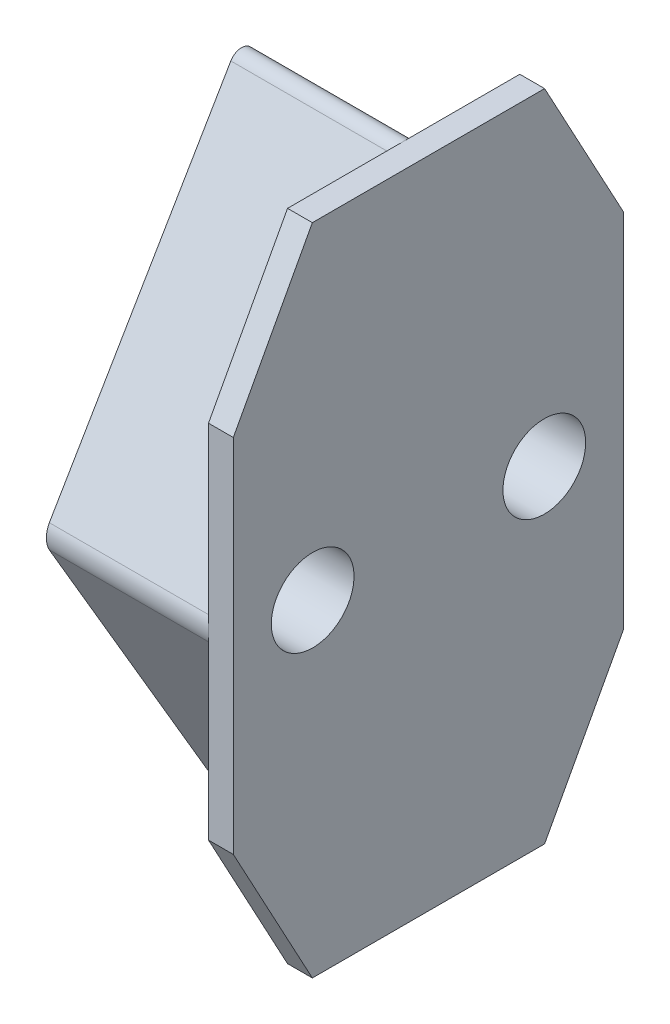
SolidWorks part; units mm, degrees
ref_plane "Front" through (0, 0, 0) normal (0, 0, 1) x (1, 0, 0)
ref_plane "Top" through (0, 0, 0) normal (0, 1, 0) x (1, 0, 0)
ref_plane "Right" through (0, 0, 0) normal (1, 0, 0) x (0, 0, -1)
sketch "Sketch1" plane through (0, 0, 0) normal (1, 0, 0) x (0, 0, -1)
  line L1 (0, -28.2575) -> (15.24, 0)
  line L2 (0, -28.2575) -> (-15.24, 0)
  line L3 (-15.24, 0) -> (0, 28.2575)
  line L4 (15.24, 0) -> (0, 28.2575)
  line L5 (0, -28.2575) -> (0, 28.2575) construction
  line L6 (-15.24, 0) -> (15.24, 0) construction
  point P0 (0, 0)
  dimension "D1" = 30.48
  dimension "D2" = 56.515
extrude "Boss-Extrude1" add sketch "Sketch1" along normal blind 12.446
sketch "Sketch6" plane through (12.446, 0, 0) normal (1, 0, 0) x (0, 0, -1)
  line L14 (-22.4547, 0) -> (0, -41.6347)
  line L15 (0, -41.6347) -> (22.4547, 0)
  line L16 (22.4547, 0) -> (0, 41.6347)
  line L17 (0, 41.6347) -> (-22.4547, 0)
  line L18 (-22.4547, 0) -> (0, -41.6347)
  line L19 (0, -41.6347) -> (22.4547, 0)
  line L20 (22.4547, 0) -> (0, 41.6347)
  line L21 (0, 41.6347) -> (-22.4547, 0)
  dimension "D1" = 6.35
extrude "Boss-Extrude3" add sketch "Sketch6" along normal blind 1.905
fillet "Fillet1" radius 1.905 8 edges at (13.3985, 41.6347, 0) (13.3985, 0, 22.4547) (13.3985, -41.6347, 0) (13.3985, 0, -22.4547) (6.223, -28.2575, 0) (6.223, 0, -15.24) (6.223, 0, 15.24) (6.223, 28.2575, 0)
sketch "Sketch7" plane through (0, 0, 0) normal (0, 1, 0) x (1, 0, 0)
  line L0 (0, 0) -> (25.2725, 0) construction
  line L1 (14.351, 0) -> (14.351, -10.3712) construction
  line L3 (4.826, -1.905) -> (4.826, 1.905) construction
  line L4 (1.651, -1.905) -> (1.651, 1.905)
  line L5 (8.001, -1.905) -> (8.001, 1.905)
  line L6 (14.351, -1.6767) -> (14.351, 1.6767) construction
  arc A1 (1.651, -1.905) -> (8.001, -1.905) centre (4.826, -1.905) ccw
  arc A2 (8.001, 1.905) -> (1.651, 1.905) centre (4.826, 1.905) ccw
  point P7 (4.826, 0)
  dimension "D1" = 6.35
  dimension "D2" = 10.16
  dimension "D3" = 6.35
revolve "Cut-Revolve2" [suppressed] cut sketch "Sketch7" angle 360 about L1
sketch "Sketch8" plane through (14.351, 0, 0) normal (1, 0, 0) x (0, 0, -1)
  line L0 (0, 0) -> (8.89, 0) construction
  line L1 (0, 0) -> (0, 3.2594) construction
  circle A0 centre (8.89, 0) radius 3.937
  circle A1 centre (-8.89, 0) radius 3.937
  dimension "D2" = 7.874
  dimension "D1" = 8.89
extrude "Cut-Extrude3" [suppressed] cut sketch "Sketch8" against normal blind 5.08
sketch "Sketch9" [suppressed] plane through (9.271, 0, 0) normal (1, 0, 0) x (0, 0, -1)
  line L0 (0, 0) -> (0, 4.0921) construction
  circle A0 centre (8.89, 0) radius 2.5527
  circle A1 centre (-8.89, 0) radius 2.5527
  dimension "D1" = 5.1054
extrude "Cut-Extrude4" [suppressed] cut sketch "Sketch9" against normal through all
sketch "Sketch10" [suppressed] plane through (15.875, 0, 0) normal (1, 0, 0) x (0, 0, -1)
  line L0 (0, 0) -> (0, 8.2156) construction
  line L1 (13.6525, 2.7496) -> (8.89, 5.4993)
  line L2 (8.89, 5.4993) -> (4.1275, 2.7496)
  line L3 (4.1275, 2.7496) -> (4.1275, -2.7496)
  line L4 (4.1275, -2.7496) -> (8.89, -5.4993)
  line L5 (8.89, -5.4993) -> (13.6525, -2.7496)
  line L6 (13.6525, -2.7496) -> (13.6525, 2.7496)
  line L7 (-13.6525, -2.7496) -> (-13.6525, 2.7496)
  line L8 (-8.89, -5.4993) -> (-13.6525, -2.7496)
  line L9 (-4.1275, -2.7496) -> (-8.89, -5.4993)
  line L10 (-4.1275, 2.7496) -> (-4.1275, -2.7496)
  line L11 (-8.89, 5.4993) -> (-4.1275, 2.7496)
  line L12 (-13.6525, 2.7496) -> (-8.89, 5.4993)
  circle A0 centre (8.89, 0) radius 4.7625 construction
  circle A1 centre (-8.89, 0) radius 4.7625 construction
  point P1 (13.6525, 0)
  dimension "D1" = 9.525
sketch "Sketch11" plane through (14.351, 0, 0) normal (1, 0, 0) x (0, 0, -1)
  line L0 (0, 0) -> (8.89, 0) construction
  line L1 (0, 0) -> (0, 10.0261) construction
  circle A0 centre (8.89, 0) radius 3.175
  circle A1 centre (-8.89, 0) radius 3.175
  dimension "D2" = 6.35
  dimension "D1" = 8.89
extrude "Cut-Extrude6" cut sketch "Sketch11" against normal through all
sketch "Sketch12" plane through (12.446, 0, 0) normal (-1, 0, 0) x (0, 0, 1)
  line L0 (-14.9806, -13.8581) -> (-14.9806, 13.8581)
  line L1 (-1.6767, -38.5258) -> (-21.9669, -0.9043) construction
  line L2 (-21.9669, 0.9043) -> (-1.6767, 38.5258) construction
  line L4 (14.9806, -13.8581) -> (14.9806, 13.8581)
  line L5 (21.9669, -0.9043) -> (1.6767, -38.5258) construction
  line L6 (1.6767, 38.5258) -> (21.9669, 0.9043) construction
  line L7 (-14.9806, -13.8581) -> (-21.9669, -0.9043)
  line L8 (21.9669, -0.9043) -> (14.9806, -13.8581)
  line L9 (14.9806, 13.8581) -> (21.9669, 0.9043)
  line L10 (-21.9669, 0.9043) -> (-14.9806, 13.8581)
  arc A0 (-14.7523, 0.9043) -> (-14.7523, -0.9043) centre (-13.0756, 0) ccw construction
  arc A3 (21.9669, -0.9043) -> (21.9669, 0.9043) centre (20.2903, 0) ccw construction
  arc A4 (-21.9669, 0.9043) -> (-21.9669, -0.9043) centre (-20.2903, 0) ccw construction
  arc A5 (21.9669, -0.9043) -> (21.9669, 0.9043) centre (20.2903, 0) ccw
  arc A6 (-21.9669, 0.9043) -> (-21.9669, -0.9043) centre (-20.2903, 0) ccw
  arc A8 (14.7523, -0.9043) -> (14.7523, 0.9043) centre (13.0756, 0) ccw construction
  point P7 (-14.9806, 0)
  point P11 (14.9806, 0)
extrude "Cut-Extrude7" cut sketch "Sketch12" against normal through all
sketch "Sketch13" [suppressed] plane through (9.271, 0, 0) normal (1, 0, 0) x (0, 0, -1)
  line L1 (5.8927, 2.5527) -> (11.8873, 2.5527)
  line L3 (5.8927, -2.5527) -> (11.8873, -2.5527)
  line L5 (-11.8873, 2.5527) -> (-5.8927, 2.5527)
  line L7 (-11.8873, -2.5527) -> (-5.8927, -2.5527)
  circle A0 centre (8.89, 0) radius 3.937 construction
  circle A1 centre (8.89, 0) radius 3.937 construction
  circle A2 centre (-8.89, 0) radius 3.937 construction
  circle A3 centre (-8.89, 0) radius 2.5527 construction
  circle A4 centre (8.89, 0) radius 2.5527 construction
  circle A5 centre (-8.89, 0) radius 3.937 construction
  arc A6 (5.8927, 2.5527) -> (5.8927, -2.5527) centre (8.89, 0) ccw
  arc A7 (-11.8873, 2.5527) -> (-11.8873, -2.5527) centre (-8.89, 0) ccw
  arc A8 (-5.8927, -2.5527) -> (-5.8927, 2.5527) centre (-8.89, 0) ccw
  arc A9 (11.8873, -2.5527) -> (11.8873, 2.5527) centre (8.89, 0) ccw
extrude "Cut-Extrude8" [suppressed] cut sketch "Sketch13" against normal blind 0.2
sketch "Sketch14" [suppressed] plane through (9.071, 0, 0) normal (1, 0, 0) x (0, 0, -1)
  line L0 (11.8873, 2.5527) -> (5.8927, 2.5527) construction
  line L1 (6.3373, 2.5527) -> (11.4427, 2.5527)
  line L2 (6.3373, 2.5527) -> (6.3373, -2.5527)
  line L3 (6.3373, -2.5527) -> (11.4427, -2.5527)
  line L4 (11.4427, 2.5527) -> (11.4427, -2.5527)
  line L5 (8.89, -2.5527) -> (11.8873, -2.5527) construction
  line L6 (-5.8927, 2.5527) -> (-11.8873, 2.5527) construction
  line L7 (-11.4427, 2.5527) -> (-6.3373, 2.5527)
  line L8 (-11.4427, 2.5527) -> (-11.4427, -2.5527)
  line L9 (-11.4427, -2.5527) -> (-6.3373, -2.5527)
  line L10 (-6.3373, 2.5527) -> (-6.3373, -2.5527)
  line L11 (-11.8873, -2.5527) -> (-5.8927, -2.5527) construction
  arc A0 (-8.89, 2.5527) -> (-8.89, -2.5527) centre (-8.89, 0) ccw construction
  arc A1 (-8.89, -2.5527) -> (-8.89, 2.5527) centre (-8.89, 0) ccw construction
  arc A2 (8.89, 2.5527) -> (8.89, -2.5527) centre (8.89, 0) ccw construction
  arc A3 (8.89, -2.5527) -> (8.89, 2.5527) centre (8.89, 0) ccw construction
extrude "Cut-Extrude9" [suppressed] cut sketch "Sketch14" against normal blind 0.2
sketch "Sketch15" plane through (0, 0, 0) normal (-1, 0, 0) x (0, 0, 1)
  line L0 (-14.7523, -0.9043) -> (0, -26.035)
  line L1 (0, -26.035) -> (14.7523, -0.9043)
  line L2 (14.7523, 0.9043) -> (0, 26.035)
  line L3 (0, 26.035) -> (-14.7523, 0.9043)
  line L4 (1.6767, 25.1486) -> (14.7523, 0.9043) construction
  line L5 (-14.7523, 0.9043) -> (-1.6767, 25.1486) construction
  line L6 (-14.7523, 0.9043) -> (-1.6767, 25.1486)
  line L7 (1.6767, 25.1486) -> (14.7523, 0.9043)
  line L16 (14.7523, -0.9043) -> (1.6767, -25.1486) construction
  line L17 (-1.6767, -25.1486) -> (-14.7523, -0.9043) construction
  line L18 (-1.6767, -25.1486) -> (-14.7523, -0.9043)
  line L19 (14.7523, -0.9043) -> (1.6767, -25.1486)
  arc A4 (1.6767, 25.1486) -> (-1.6767, 25.1486) centre (0, 24.2443) ccw construction
  arc A5 (1.6767, 25.1486) -> (-1.6767, 25.1486) centre (0, 24.2443) ccw
  arc A7 (-1.6767, -25.1486) -> (1.6767, -25.1486) centre (0, -24.2443) ccw construction
  arc A18 (-1.6767, -25.1486) -> (1.6767, -25.1486) centre (0, -24.2443) ccw
  dimension "D1" = 52.07
extrude "Cut-Extrude10" cut sketch "Sketch15" against normal up to surface (12.446 mm away) up to face at (12.446, 15.8904, 0)
fillet "Fillet3" radius 0.9525 2 edges at (6.223, -26.035, 0) (6.223, 26.035, 0)
sketch "Sketch16" plane through (12.446, 0, 0) normal (-1, 0, 0) x (0, 0, 1)
  line L0 (-8.9143, -25.106) -> (8.9143, -25.106)
  line L1 (14.9806, -13.8581) -> (1.6767, -38.5258) construction
  line L2 (0, 0) -> (12.6414, 0) construction
  line L3 (-8.9143, 25.106) -> (8.9143, 25.106)
  line L4 (-14.9806, 13.8581) -> (-1.6767, 38.5258) construction
  line L5 (1.6767, 38.5258) -> (14.9806, 13.8581) construction
  line L6 (-1.6767, -38.5258) -> (-14.9806, -13.8581) construction
  line L7 (-8.9143, 25.106) -> (-1.6767, 38.5258)
  line L8 (1.6767, 38.5258) -> (8.9143, 25.106)
  line L9 (-1.6767, -38.5258) -> (-8.9143, -25.106)
  line L10 (8.9143, -25.106) -> (1.6767, -38.5258)
  line L12 (0, 0) -> (0, 12.975) construction
  line L14 (-1.6767, -38.5258) -> (-8.9143, -25.106)
  line L17 (-8.9143, 25.106) -> (-1.6767, 38.5258)
  arc A1 (1.6767, 38.5258) -> (-1.6767, 38.5258) centre (0, 37.6215) ccw construction
  arc A2 (-1.6767, -38.5258) -> (1.6767, -38.5258) centre (0, -37.6215) ccw construction
  arc A3 (1.6767, 38.5258) -> (-1.6767, 38.5258) centre (0, 37.6215) ccw
  arc A4 (-1.6767, -38.5258) -> (1.6767, -38.5258) centre (0, -37.6215) ccw
  arc A9 (-0.8214, -24.6357) -> (0.8214, -24.6357) centre (0, -24.1535) ccw construction
  point P3 (0, -25.106)
  point P21 (-13.7106, 0)
  line M8 (-1.6767, 38.5258) -> (-14.9806, 13.8581)
  line M14 (14.9806, 13.8581) -> (1.6767, 38.5258)
  arc M15 (1.6767, 38.5258) -> (-1.6767, 38.5258) centre (0, 37.6215) ccw
extrude "Cut-Extrude11" cut sketch "Sketch16" against normal through all contours L3 M8 M14 M15 | L9 A4 L10 L0
